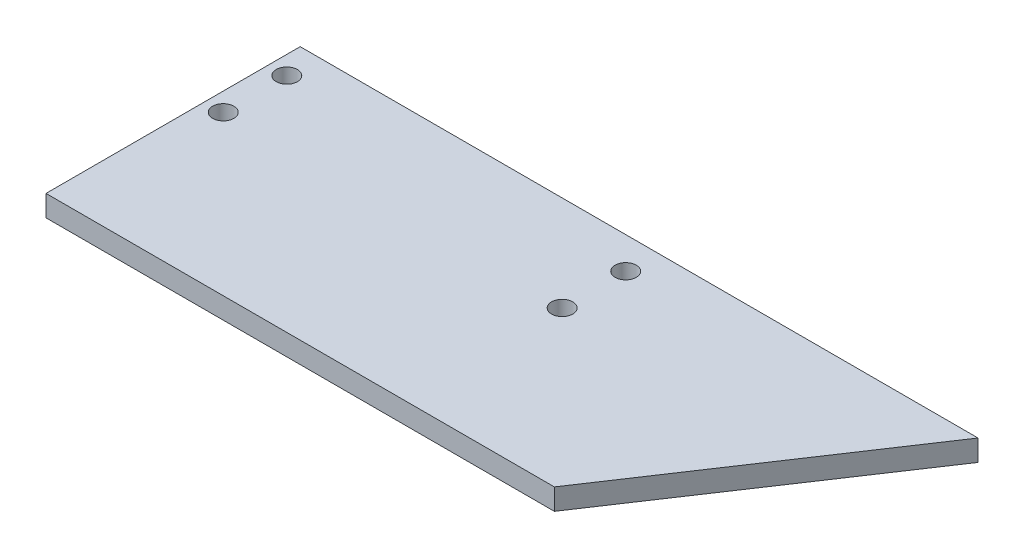
SolidWorks part; units mm, degrees
ref_plane "Front Plane" through (0, 0, 0) normal (0, 0, 1) x (1, 0, 0)
ref_plane "Top Plane" through (0, 0, 0) normal (0, 1, 0) x (1, 0, 0)
ref_plane "Right Plane" through (0, 0, 0) normal (1, 0, 0) x (0, 0, -1)
sketch "Sketch1" plane through (0, 0, 0) normal (0, 1, 0) x (1, 0, 0)
  line L0 (116.1143, 43.5429) -> (65.3143, -32.6571)
  line L1 (-87.0857, -32.6571) -> (65.3143, -32.6571)
  line L2 (-87.0857, -32.6571) -> (-87.0857, 43.5429)
  line L3 (-87.0857, 43.5429) -> (116.1143, 43.5429)
  line L5 (-87.0857, -32.6571) -> (116.1143, 43.5429) construction
  line L6 (-87.0857, 43.5429) -> (65.3143, -32.6571) construction
  circle A1 centre (20.0251, 34.0179) radius 3.175
  circle A2 centre (20.0251, 14.9679) radius 3.175
  circle A3 centre (-81.5749, 34.0179) radius 3.175
  circle A4 centre (-81.5749, 14.9679) radius 3.175
  point P0 (0, 0)
  point P1 (0, 0)
  point P4 (0, 0)
  point P6 (112.8547, 40.3933)
  point P7 (142.2659, 38.6722)
  point P8 (145.4407, 30.8037)
  point P19 (133.487, 45.3653)
  point P20 (55.8568, -37.4165)
  point P21 (0, 0)
  point P22 (98.4704, -10.3895)
  point P23 (96.3481, 3.5884)
  point P24 (0, 0)
  point P25 (130.4972, 45.0693)
  dimension "D1" = 203.2
  dimension "D6" = 6.35
  dimension "D7" = 6.35
  dimension "D2" = 76.2
  dimension "D3" = 152.4
  dimension "D5" = 101.6
  dimension "D8" = 19.05
  dimension "D9" = 9.525
extrude "Boss-Extrude1" add sketch "Sketch1" along normal blind 6.35
